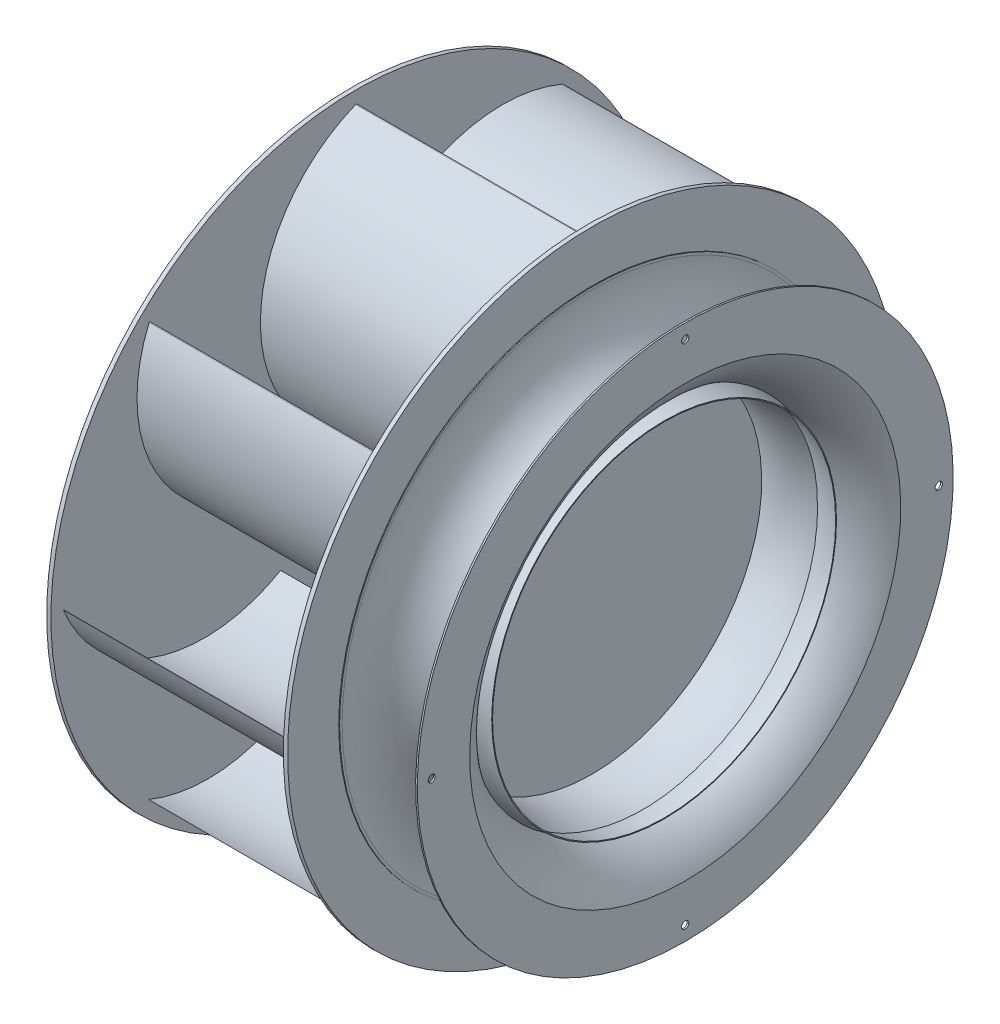
SolidWorks part; units mm, degrees
ref_plane "Front Plane" through (0, 0, 0) normal (0, 0, 1) x (1, 0, 0)
ref_plane "Top Plane" through (0, 0, 0) normal (0, 1, 0) x (1, 0, 0)
ref_plane "Right Plane" through (0, 0, 0) normal (1, 0, 0) x (0, 0, -1)
sketch "Sketch1" plane through (0, 0, 0) normal (0, 0, 1) x (1, 0, 0)
  line L0 (0, 0) -> (831.9083, 0) construction
  line L1 (0, 0) -> (0, 109)
  line L2 (5, 114) -> (70, 114)
  line L3 (70, 114) -> (70, 138)
  line L4 (70, 138) -> (90, 138)
  line L5 (90, 138) -> (90, 98)
  line L6 (90, 98) -> (92, 98)
  line L7 (92, 98) -> (92, 133)
  line L8 (92, 133) -> (95, 133)
  line L9 (95, 133) -> (95, 98)
  line L10 (95, 98) -> (97, 98)
  line L11 (97, 98) -> (97, 0)
  line L12 (97, 0) -> (0, 0)
  arc A0 (5, 114) -> (0, 109) centre (5, 109) ccw
  point P16 (0, 114)
  dimension "D10" = 5
  dimension "D1" = 114
  dimension "D2" = 24
  dimension "D3" = 70
  dimension "D4" = 40
  dimension "D5" = 35
  dimension "D6" = 2
  dimension "D7" = 20
  dimension "D8" = 3
  dimension "D9" = 27
revolve "Revolve1" add sketch "Sketch1" angle 360 about L0
sketch "Sketch2" plane through (97, 0, 0) normal (1, 0, 0) x (0, 0, -1)
  circle A0 centre (0, 0) radius 360.5
  dimension "D1" = 721
extrude "Extrude1" add sketch "Sketch2" along normal blind 5
sketch "Sketch9" plane through (97, 0, 0) normal (-1, 0, 0) x (0, 0, 1)
  circle A0 centre (0, 0) radius 355.5
  circle A1 centre (0, 0) radius 100
  circle A2 centre (0, 0) radius 360.5 construction
  dimension "D1" = 5
  dimension "D2" = 200
extrude "Extrude7" cut sketch "Sketch9" against normal blind 3
ref_plane "Plane1" through (377, 0, 0) normal (1, 0, 0) x (0, 0, -1)
sketch "Sketch3" plane through (377, 0, 0) normal (1, 0, 0) x (0, 0, -1)
  circle A0 centre (0, 0) radius 360.5
  dimension "D1" = 721
extrude "Extrude2" add sketch "Sketch3" along normal blind 5 separate body
sketch "Sketch4" plane through (102, 0, 0) normal (1, 0, 0) x (0, 0, -1)
  line L0 (0, 0) -> (0, 345.5) construction
  line L1 (0, 0) -> (254.912, 254.912) construction
  line L2 (0, 125) -> (0.866, 124.5)
  line L3 (244.3054, 244.3054) -> (245.1714, 243.8054)
  circle A0 centre (0, 0) radius 345.5 construction
  circle A1 centre (0, 0) radius 360.5 construction
  circle A2 centre (0, 0) radius 125 construction
  arc A3 (0, 125) -> (244.3054, 244.3054) centre (173.926, 78.6348) cw
  arc A4 (0.866, 124.5) -> (245.1714, 243.8054) centre (174.7921, 78.1348) cw
  dimension "D1" = 15
  dimension "D2" = 250
  dimension "D6" = 180
  dimension "D7" = 180
  dimension "D3" = 45
  dimension "D4" = 60
  dimension "D5" = 1
extrude "Extrude3" add sketch "Sketch4" along normal up to surface (280 mm away) up to face at (382, 0, -360.5)
ref_axis "Axis1" through (253.5503, 0, 0) along (-1, 0, 0)
pattern_circular "CirPattern1" count 8 over 360 about axis through (253.5503, 0, 0) along (-1, 0, 0) of "Extrude3"
sketch "Sketch5" plane through (0, 0, 0) normal (0, 0, 1) x (1, 0, 0)
  line L0 (0, 0) -> (527.2916, 0) construction
  line L1 (253.5503, 0) -> (75.411, 0) construction
  line L2 (382, 300) -> (383, 300)
  line L3 (383, 300) -> (383, 297)
  line L4 (382, 300) -> (382, 297)
  line L5 (467, 204) -> (467, 203)
  line L6 (70, 138) -> (70, -138) construction
  line L7 (382, -360.5) -> (382, 360.5) construction
  arc A0 (383, 297) -> (467, 204) centre (467.6225, 288.9977) ccw
  arc A1 (382, 297) -> (467, 203) centre (466.522, 287.9987) ccw
  dimension "D7" = 85
  dimension "D8" = 85
  dimension "D1" = 203
  dimension "D2" = 1
  dimension "D3" = 1
  dimension "D4" = 3
  dimension "D5" = 300
  dimension "D6" = 397
revolve "Revolve2" add sketch "Sketch5" angle 360 about L0
ref_plane "Plane3" through (492, 0, 0) normal (1, 0, 0) x (0, 0, -1)
sketch "Sketch6" plane through (0, 0, 0) normal (0, 0, 1) x (1, 0, 0)
  line L0 (492, 317) -> (490, 317)
  line L1 (492, -251.35) -> (492, 251.35) construction
  line L2 (490, 317) -> (490, 255)
  line L3 (0, 0) -> (615.1417, 0) construction
  line L4 (0, 114) -> (0, -114) construction
  line L5 (253.5503, 0) -> (75.411, 0) construction
  line L6 (492, 317) -> (492, 255)
  line L7 (375, 203) -> (379, 203)
  line L8 (375, 203) -> (375, 201)
  line L9 (375, 201) -> (379, 201)
  arc A0 (379, 203) -> (490, 255) centre (400.9789, 300.5548) ccw
  arc A1 (379, 201) -> (492, 255) centre (401.883, 298.3466) ccw
  dimension "D7" = 100
  dimension "D8" = 100
  dimension "D1" = 317
  dimension "D2" = 2
  dimension "D3" = 255
  dimension "D4" = 117
  dimension "D5" = 203
  dimension "D6" = 4
revolve "Revolve3" add sketch "Sketch6" angle 360 about L3
sketch "Sketch7" plane through (492, 0, 0) normal (1, 0, 0) x (0, 0, -1)
  line L0 (0, 0) -> (0, 300) construction
  circle A0 centre (0, 0) radius 300 construction
  circle A1 centre (0, 300) radius 4.25
  dimension "D1" = 600
  dimension "D2" = 8.5
extrude "Extrude5" cut sketch "Sketch7" against normal blind 5
pattern_circular "CirPattern2" count 4 over 360 about axis through (253.5503, 0, 0) along (-1, 0, 0) of "Extrude5"
sketch "Sketch8" plane through (0, 0, 0) normal (1, 0, 0) x (0, 0, -1)
  line L0 (0, 0) -> (0, 126) construction
  circle A0 centre (0, 0) radius 126 construction
  circle A1 centre (0, 126) radius 5
  dimension "D1" = 252
  dimension "D2" = 10
extrude "Extrude6" cut sketch "Sketch8" along normal up to surface (90 mm away) up to face at (90, 0, 138)
pattern_circular "CirPattern3" count 8 over 360 about axis through (253.5503, 0, 0) along (-1, 0, 0) of "Extrude6"
